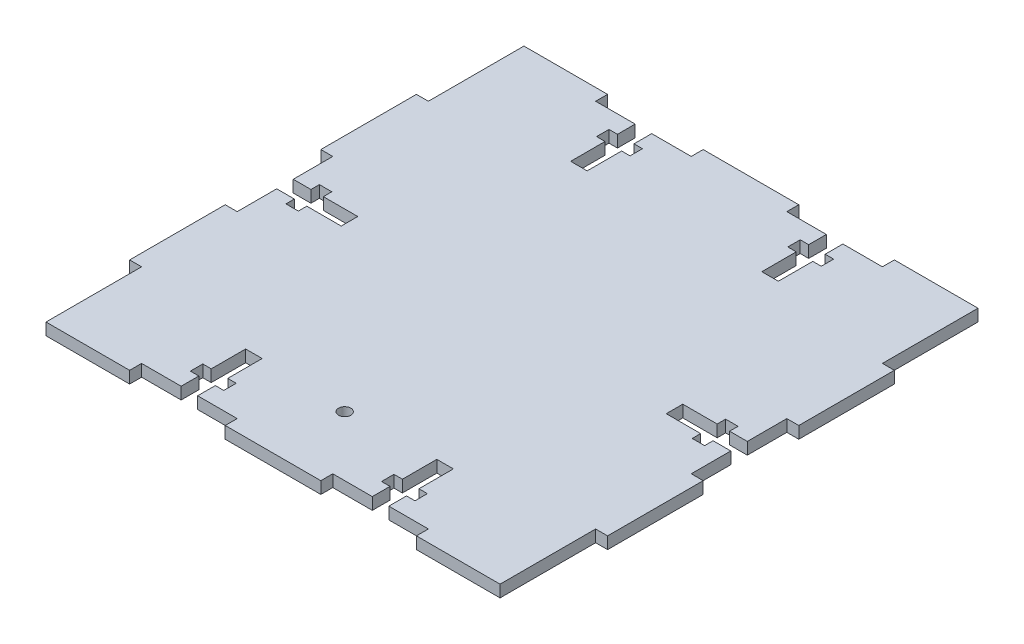
SolidWorks part; units mm, degrees
ref_plane "Front Plane" through (0, 0, 0) normal (0, 0, 1) x (1, 0, 0)
ref_plane "Top Plane" through (0, 0, 0) normal (0, 1, 0) x (1, 0, 0)
ref_plane "Right Plane" through (0, 0, 0) normal (1, 0, 0) x (0, 0, -1)
sketch "Sketch1" plane through (0, 0, 0) normal (0, 1, 0) x (1, 0, 0)
  line L1 (0, 0) -> (127, 0)
  line L2 (0, 0) -> (0, 127)
  line L3 (0, 127) -> (127, 127)
  line L4 (127, 0) -> (127, 127)
  dimension "D1" = 127
  dimension "D2" = 127
extrude "Boss-Extrude1" add sketch "Sketch1" along normal blind 3.175
sketch "Sketch2" plane through (0, 3.175, 0) normal (0, 1, 0) x (1, 0, 0)
  line L1 (0, 127) -> (3.175, 127)
  line L2 (0, 127) -> (0, 101.6)
  line L3 (0, 101.6) -> (3.175, 101.6)
  line L4 (3.175, 127) -> (3.175, 101.6)
  dimension "D1" = 25.4
  dimension "D2" = 3.175
extrude "Cut-Extrude1" cut sketch "Sketch2" against normal blind 6.35
pattern_linear "LPattern1" count 3 spacing 50.8 along (0, 0, 1) count 2 spacing 123.825 along (1, 0, 0) of "Cut-Extrude1"
sketch "Sketch3" plane through (0, 3.175, 0) normal (0, 1, 0) x (1, 0, 0)
  line L0 (3.175, 0) -> (123.825, 0) construction
  line L1 (25.4, 0) -> (50.8, 0)
  line L2 (25.4, 0) -> (25.4, 3.175)
  line L3 (25.4, 3.175) -> (50.8, 3.175)
  line L4 (50.8, 0) -> (50.8, 3.175)
  line L5 (0, 50.8) -> (0, 25.4) construction
  dimension "D1" = 25.4
  dimension "D2" = 3.175
  dimension "D3" = 25.4
extrude "Cut-Extrude2" cut sketch "Sketch3" against normal blind 6.35
pattern_linear "LPattern2" count 3 spacing 50.8 along (1, 0, 0) count 2 spacing 123.825 along (0, 0, -1) of "Cut-Extrude2"
ref_plane "Plane1" through (0, 0, -63.5) normal (0, 0, 1) x (1, 0, 0)
sketch "Sketch4" plane through (0, 3.175, 0) normal (0, 1, 0) x (1, 0, 0)
  line L0 (123.825, 76.2) -> (123.825, 50.8) construction
  line L1 (123.825, 65.6971) -> (106.68, 65.6971)
  line L2 (123.825, 65.6971) -> (123.825, 61.3029)
  line L3 (123.825, 61.3029) -> (106.68, 61.3029)
  line L4 (106.68, 65.6971) -> (106.68, 61.3029)
  line L5 (127, 76.2) -> (123.825, 76.2) construction
  line L7 (115.824, 67.945) -> (119.126, 67.945)
  line L8 (115.824, 67.945) -> (115.824, 59.055)
  line L9 (115.824, 59.055) -> (119.126, 59.055)
  line L10 (119.126, 67.945) -> (119.126, 59.055)
  point P6 (123.825, 63.5)
  point P13 (117.475, 59.055)
  point P14 (119.126, 63.5)
  dimension "D1" = 17.145
  dimension "D2" = 4.3942
  dimension "D3" = 12.7
  dimension "D4" = 3.302
  dimension "D5" = 6.35
  dimension "D6" = 8.89
  dimension "D7" = 12.7
extrude "Cut-Extrude3" cut sketch "Sketch4" against normal blind 8.89 contours L1 L4 L3 L2 | L7 L10 L9 L8
sketch "Sketch5" plane through (0, 3.175, 0) normal (0, 1, 0) x (1, 0, 0)
  line L0 (50.8, 3.175) -> (25.4, 3.175) construction
  line L1 (35.9029, 3.175) -> (40.2971, 3.175)
  line L2 (35.9029, 3.175) -> (35.9029, 20.32)
  line L3 (35.9029, 20.32) -> (40.2971, 20.32)
  line L4 (40.2971, 3.175) -> (40.2971, 20.32)
  line L5 (50.8, 0) -> (50.8, 3.175) construction
  line L6 (33.655, 11.176) -> (42.545, 11.176)
  line L7 (33.655, 11.176) -> (33.655, 7.874)
  line L8 (33.655, 7.874) -> (42.545, 7.874)
  line L9 (42.545, 11.176) -> (42.545, 7.874)
  point P6 (38.1, 20.32)
  point P12 (38.1, 7.874)
  point P15 (42.545, 9.525)
  dimension "D1" = 17.145
  dimension "D2" = 4.3942
  dimension "D3" = 12.7
  dimension "D4" = 3.302
  dimension "D5" = 8.89
  dimension "D6" = 12.7
  dimension "D7" = 6.35
extrude "Cut-Extrude4" cut sketch "Sketch5" against normal blind 30.48 contours L3 L4 L1 L2 | L7 L8 L9 L6
pattern_linear "LPattern3" count 2 spacing 50.8 along (1, 0, 0) of "Cut-Extrude4"
sketch "Sketch10" plane through (0, 3.175, 0) normal (0, 1, 0) x (1, 0, 0)
  line L1 (78.7908, 104.775) -> (101.6, 104.775)
  line L2 (78.7908, 104.775) -> (78.7908, 48.8442)
  line L3 (78.7908, 48.8442) -> (101.6, 48.8442)
  line L4 (101.6, 104.775) -> (101.6, 48.8442)
  line L5 (76.2, 123.825) -> (101.6, 123.825) construction
  line L6 (127, 76.2) -> (127, 101.6) construction
  dimension "D1" = 22.8092
  dimension "D2" = 55.9308
  dimension "D3" = 25.4
  dimension "D4" = 19.05
mirror "Mirror2" about plane through (0, 0, -63.5) normal (0, 0, 1) of "LPattern3"
sketch "2x2_PCB" plane through (0, 3.175, 0) normal (0, 1, 0) x (1, 0, 0)
  line L0 (106.68, 65.6971) -> (106.68, 61.3029) construction
  line L1 (10.16, 90.551) -> (60.96, 90.551)
  line L2 (10.16, 90.551) -> (10.16, 36.449)
  line L3 (10.16, 36.449) -> (60.96, 36.449)
  line L4 (60.96, 90.551) -> (60.96, 36.449)
  line L5 (10.16, 90.551) -> (60.96, 36.449) construction
  line L6 (10.16, 36.449) -> (60.96, 90.551) construction
  line L8 (0, 101.6) -> (0, 76.2) construction
  point P0 (35.56, 63.5)
  point P7 (106.68, 63.5)
  point P8 (35.56, 90.551)
  dimension "D1" = 50.8
  dimension "D2" = 54.102
  dimension "D3" = 35.56
hole_wizard "#4 Clearance Hole4" positions "Sketch18" profile "Sketch16" hole size "#4" standard "ANSI Inch"
sketch "Sketch18" plane through (0, 3.175, 0) normal (0, 1, 0) x (1, 0, 0)
  line L0 (127, 25.4) -> (127, 50.8) construction
  line L2 (50.8, 0) -> (76.2, 0) construction
  point P0 (63.5, 19.05)
  dimension "D1" = 63.5
  dimension "D2" = 19.05
sketch "Sketch16" plane through (63.5, 3.175, -19.05) normal (1, 0, 0) x (0, 0, 1)
  line L0 (0, 0) -> (0, 11.1406)
  line L1 (0, 11.1406) -> (1.6319, 10.16)
  line L2 (1.6319, 10.16) -> (1.6319, 0)
  line L5 (1.6319, 0) -> (0, 0)
  line L10 (0, 11.1406) -> (-1.632, 10.16) construction
  line L11 (0, -6.35) -> (0, 107.95) construction
  dimension "Hole Dia." = 3.2639
  dimension "Hole Depth" = 10.16
  dimension "Drill Angle" = 118
ref_plane "Plane2" through (63.5, 0, 0) normal (-1, 0, 0) x (0, 0, 1)
mirror "Mirror3" about plane through (63.5, 0, 0) normal (-1, 0, 0) of "Cut-Extrude3"
sketch "Sketch19" plane through (0, 3.175, 0) normal (0, 1, 0) x (1, 0, 0)
  line L1 (13.9003, 102.0174) -> (115.5003, 102.0174)
  line L2 (13.9003, 102.0174) -> (13.9003, 25.8174)
  line L3 (13.9003, 25.8174) -> (115.5003, 25.8174)
  line L4 (115.5003, 102.0174) -> (115.5003, 25.8174)
  dimension "D1" = 101.6
  dimension "D2" = 76.2
